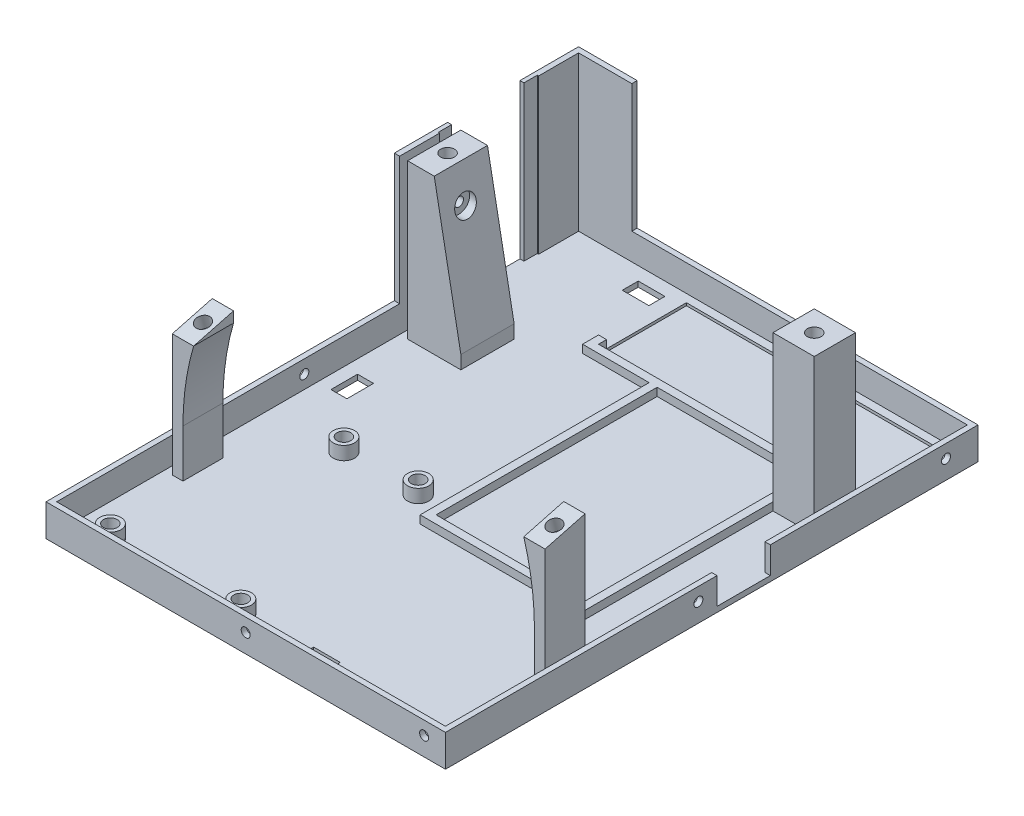
SolidWorks part; units mm, degrees
ref_plane "Front Plane" through (0, 0, 0) normal (0, 0, 1) x (1, 0, 0)
ref_plane "Top Plane" through (0, 0, 0) normal (0, 1, 0) x (1, 0, 0)
ref_plane "Right Plane" through (0, 0, 0) normal (1, 0, 0) x (0, 0, -1)
other "Configuration Table"
sketch "Sketch1" plane through (0, 0, 0) normal (0, 1, 0) x (1, 0, 0)
  line L1 (75, -100) -> (-75, -100)
  line L2 (75, -100) -> (75, 100)
  line L3 (75, 100) -> (-75, 100)
  line L4 (-75, -100) -> (-75, 100)
  line L5 (75, -100) -> (-75, 100) construction
  line L6 (75, 100) -> (-75, -100) construction
  point P0 (0, 0)
  dimension "D1" = 200
  dimension "D2" = 150
extrude "Boss-Extrude1" add sketch "Sketch1" along normal blind 2
sketch "Sketch2" plane through (0, 2, 0) normal (0, 1, 0) x (1, 0, 0)
  line L0 (75, 80) -> (-55, 80) construction
  line L1 (75, -100) -> (75, 100) construction
  line L2 (-55, 80) -> (-55, -100) construction
  line L3 (-75, -100) -> (75, -100) construction
  line L4 (75, 100) -> (-75, 100) construction
  line L5 (-65, -100) -> (-65, 100) construction
  line L6 (-75, 100) -> (-75, -100) construction
  line L7 (75, 90) -> (-75, 90) construction
  line L8 (-75, -80) -> (75, -80) construction
  line L9 (-75, -90) -> (75, -90) construction
  line L10 (-75, -100) -> (75, -100) construction
  line L11 (-62, 0) -> (-68, 0)
  line L12 (-62, 0) -> (-62, 10)
  line L13 (-62, 10) -> (-68, 10)
  line L14 (-68, 0) -> (-68, 10)
  line L15 (-62, 0) -> (-68, 10) construction
  line L16 (-62, 10) -> (-68, 0) construction
  line L18 (12.5, -93) -> (22.5, -93)
  line L19 (12.5, -93) -> (12.5, -87)
  line L20 (12.5, -87) -> (22.5, -87)
  line L21 (22.5, -93) -> (22.5, -87)
  line L22 (12.5, -93) -> (22.5, -87) construction
  line L23 (12.5, -87) -> (22.5, -93) construction
  line L24 (-35.5887, 87) -> (-45.5887, 87)
  line L25 (-35.5887, 87) -> (-35.5887, 93)
  line L26 (-35.5887, 93) -> (-45.5887, 93)
  line L27 (-45.5887, 87) -> (-45.5887, 93)
  line L28 (-35.5887, 87) -> (-45.5887, 93) construction
  line L29 (-35.5887, 93) -> (-45.5887, 87) construction
  point P22 (-40.5887, 90)
  dimension "D7" = 6
  dimension "D10" = 10
  dimension "D1" = 20
  dimension "D2" = 20
  dimension "D3" = 10
  dimension "D4" = 10
  dimension "D5" = 20
  dimension "D6" = 10
  dimension "D8" = 6
  dimension "D9" = 100
  dimension "D11" = 10
  dimension "D12" = 6
  dimension "D13" = 10
extrude "Cut-Extrude1" cut sketch "Sketch2" against normal through all
sketch "Sketch5" plane through (0, 2, 0) normal (0, 1, 0) x (1, 0, 0)
  line L0 (-75, 100) -> (-75, -100)
  line L1 (75, 100) -> (-75, 100) construction
  line L2 (-75, 100) -> (75, 100)
  line L3 (-73, 98) -> (73, 98)
  line L4 (-75, -100) -> (75, -100) construction
  line L5 (75, -100) -> (75, 100) construction
  line L6 (75, 100) -> (75, 98)
  line L8 (-73, 98) -> (-73, -98)
  line L10 (75, -98) -> (75, -100)
  line L11 (75, -100) -> (-75, -100)
  line L12 (-73, -98) -> (73, -98)
  line L13 (73, 98) -> (73, -98)
  line L14 (75, 98) -> (75, -98)
  line L15 (-75, 100) -> (-75, -100) construction
  dimension "D1" = 0
  dimension "D2" = 0
  dimension "D3" = 2
  dimension "D4" = 2
  dimension "D5" = 2
  dimension "D6" = 2
  dimension "D7" = 0
extrude "Boss-Extrude2" add sketch "Sketch5" along normal blind 10
sketch "Sketch6" plane through (-75, 0, 0) normal (-1, 0, 0) x (0, 0, 1)
  line L1 (-80, 2) -> (100, 2) construction
  line L3 (-50.8, 2) -> (-78, 2)
  line L4 (-100, 12) -> (-100, 0) construction
  line L5 (-78, 2) -> (-78, 12)
  line L6 (-100, 12) -> (100, 12) construction
  line L7 (-78, 12) -> (-50.8, 12)
  line L8 (-50.8, 12) -> (-50.8, 2)
  dimension "D1" = 27.2
  dimension "D2" = 22
extrude "Cut-Extrude2" cut sketch "Sketch6" against normal blind 10
sketch "Sketch8" plane through (-75, 0, 0) normal (-1, 0, 0) x (0, 0, 1)
  line L2 (100, 12) -> (100, 0) construction
  circle A1 centre (5, 7) radius 1.7
  dimension "D3" = 95
extrude "Cut-Extrude4" cut sketch "Sketch8" against normal through all
sketch "Sketch10" plane through (75, 0, 0) normal (1, 0, 0) x (0, 0, -1)
  line L2 (-100, 2) -> (100, 2) construction
  line L3 (2, 2) -> (2, 12)
  line L4 (-100, 12) -> (100, 12) construction
  line L5 (2, 12) -> (22, 12)
  line L6 (22, 12) -> (22, 2)
  line L8 (2, 2) -> (22, 2)
  line L9 (-100, 12) -> (-100, 0) construction
  dimension "D1" = 20
  dimension "D2" = 102
extrude "Cut-Extrude6" cut sketch "Sketch10" against normal blind 10
sketch "Sketch12" plane through (0, 2, 0) normal (0, 1, 0) x (1, 0, 0)
  line L0 (-63, -92) -> (-9.7, -92) construction
  line L1 (56, 95) -> (56, 62) construction
  line L2 (56, 62) -> (-29, 62) construction
  line L3 (-29, 62) -> (-29, 95) construction
  line L4 (-73, -98) -> (73, -98) construction
  line L5 (-9.7, -92) -> (-9.7, -23.4) construction
  line L6 (-9.7, -23.4) -> (-63, -23.4) construction
  line L7 (73, 22) -> (73, 98) construction
  line L8 (-73, 50.8) -> (-73, -98) construction
  line L9 (-63, -23.4) -> (-63, -92) construction
  line L10 (63, -92) -> (9.3, -92) construction
  line L11 (73, -98) -> (73, 2) construction
  line L12 (9.3, -92) -> (9.3, -10.6) construction
  line L13 (9.3, -10.6) -> (63, -10.6) construction
  line L14 (63, -10.6) -> (63, -92) construction
  line L15 (-29, 95) -> (56, 95) construction
  line L16 (73, 98) -> (-73, 98) construction
  line L17 (-53.4, -92) -> (-53.4, -100) construction
  line L18 (-75, -100) -> (75, -100) construction
  line L19 (-53.4, -100) -> (-41.4, -100) construction
  line L20 (-41.4, -100) -> (-41.4, -92) construction
  line L21 (-73, 78) -> (-73, 50.8) construction
  dimension "D1" = 6
  dimension "D2" = 33
  dimension "D3" = 10
  dimension "D4" = 53.3
  dimension "D5" = 10
  dimension "D6" = 68.6
  dimension "D7" = 81.4
  dimension "D8" = 53.7
  dimension "D9" = 3
  dimension "D10" = 85
  dimension "D11" = 17
  dimension "D12" = 12
  dimension "D13" = 9.6
sketch "Sketch15" plane through (0, 0, 100) normal (0, 0, 1) x (1, 0, 0)
  line L0 (-75, 0) -> (75, 0) construction
  line L2 (75, 12) -> (75, 0) construction
  circle A0 centre (0, 7) radius 1.7
  dimension "D1" = 7
  dimension "D2" = 75
extrude "Cut-Extrude7" cut sketch "Sketch15" against normal blind 10
sketch "Sketch16" plane through (0, 0, 100) normal (0, 0, 1) x (1, 0, 0)
  line L0 (-75, 0) -> (75, 0) construction
  circle A0 centre (67, 7) radius 1.7
  dimension "D1" = 8
  dimension "D2" = 7
extrude "Cut-Extrude8" cut sketch "Sketch16" against normal blind 3
sketch "Sketch19" plane through (0, 2, 0) normal (0, 1, 0) x (1, 0, 0)
  line L0 (-7.55, -94) -> (-65.15, -94) construction
  line L1 (-63, -23.4) -> (-63, -92) construction
  line L2 (-73, -98) -> (73, -98) construction
  line L3 (-65.15, -94) -> (-65.15, 4.3) construction
  line L4 (-65.15, 4.3) -> (-7.55, 4.3) construction
  line L5 (-7.55, 4.3) -> (-7.55, -94) construction
  circle A0 centre (-60.85, -90) radius 4
  circle A1 centre (-11.85, -90) radius 4
  circle A2 centre (-45.23, -17.9) radius 4
  circle A3 centre (-17.32, -17.9) radius 4
  point P17 (0, 0)
  dimension "D6" = 4
  dimension "D8" = 37.68
  dimension "D10" = 9.77
  dimension "D1" = 2.15
  dimension "D2" = 2.15
  dimension "D3" = 4
  dimension "D4" = 4.3
  dimension "D5" = 4
  dimension "D7" = 4.3
  dimension "D9" = 72.1
extrude "Boss-Extrude3" add sketch "Sketch19" along normal blind 5
sketch "Sketch20" plane through (0, 7, 0) normal (0, 1, 0) x (1, 0, 0)
  circle A0 centre (-45.23, -17.9) radius 2.6
  circle A1 centre (-17.32, -17.9) radius 2.6
  circle A2 centre (-11.85, -90) radius 2.6
  circle A3 centre (-60.85, -90) radius 2.6
extrude "Cut-Extrude10" cut sketch "Sketch20" against normal blind 5
sketch "Sketch21" plane through (0, 2, 0) normal (0, 1, 0) x (1, 0, 0)
  line L0 (-29.5, 65) -> (-32.5, 65)
  line L1 (73, 22) -> (73, 98) construction
  line L2 (-32.5, 65) -> (-32.5, 59)
  line L3 (-32.5, 59) -> (70, 59)
  line L8 (70, 62) -> (-29.5, 62)
  line L9 (-29.5, 62) -> (-29.5, 65)
  line L12 (70, 59) -> (70, 62)
  line L15 (-29, 62) -> (-29, 95) construction
  point P4 (-29.5, 63.5)
  dimension "D1" = 3
  dimension "D2" = 3
  dimension "D3" = 3
  dimension "D4" = 0.5
  dimension "D5" = 3
extrude "Boss-Extrude4" add sketch "Sketch21" along normal blind 3
sketch "Sketch22" plane through (0, 12, 0) normal (0, 1, 0) x (1, 0, 0)
  line L0 (-75, 50.8) -> (-73, 50.8)
  line L1 (-73, 50.8) -> (-73, 30.8)
  line L2 (-75, 100) -> (-53, 100)
  line L3 (-73, 30.8) -> (-75, 30.8)
  line L4 (-75, 50.8) -> (-75, -100) construction
  line L5 (-75, 30.8) -> (-75, 50.8)
  line L7 (75, 100) -> (-75, 100) construction
  line L9 (-75, 100) -> (-75, 78) construction
  line L10 (-75, 100) -> (-75, 78)
  line L11 (-75, 78) -> (-73, 78)
  line L12 (-53, 100) -> (-53, 98)
  line L13 (73, 98) -> (-73, 98) construction
  line L14 (-53, 98) -> (-73, 98)
  line L15 (-73, 98) -> (-73, 78)
  dimension "D1" = 22
  dimension "D2" = 20
  dimension "D3" = 2
  dimension "D4" = 2
extrude "Boss-Extrude5" add sketch "Sketch22" along normal blind 48
sketch "Sketch25" plane through (0, 60, 0) normal (0, 1, 0) x (1, 0, 0)
  line L0 (-73, 78) -> (-73, 83)
  line L2 (-73, 83) -> (-73.5, 83)
  line L3 (-73.5, 83) -> (-73.5, 78)
  line L5 (-73.5, 78) -> (-73, 78)
  line L12 (-73, 50.8) -> (-73.5, 50.8)
  line L13 (-73, 50.8) -> (-75, 50.8) construction
  line L14 (-73.5, 50.8) -> (-73.5, 45.8)
  line L15 (-73.5, 45.8) -> (-73, 45.8)
  line L16 (-73, 50.8) -> (-73, -98) construction
  line L17 (-73, 45.8) -> (-73, 50.8)
  dimension "D1" = 0.5
  dimension "D2" = 5
  dimension "D3" = 5
extrude "Cut-Extrude13" cut sketch "Sketch25" against normal up to surface (58 mm away) up to face at (-17.32, 2, 21.9)
sketch "Sketch26" plane through (75, 0, 0) normal (1, 0, 0) x (0, 0, -1)
  line L0 (-100, 0) -> (100, 0) construction
  line L1 (100, 12) -> (100, 0) construction
  circle A0 centre (88, 7) radius 1.7
  point P5 (0, 0)
  dimension "D1" = 7
  dimension "D2" = 12
extrude "Cut-Extrude15" cut sketch "Sketch26" against normal blind 5
sketch "Sketch27" plane through (0, 2, 0) normal (0, 1, 0) x (1, 0, 0)
  line L0 (-70, 50.8) -> (-70, 30.8)
  line L1 (-70, 30.8) -> (-50, 30.8)
  line L2 (-50, 30.8) -> (-50, 50.8)
  line L3 (-50, 50.8) -> (-70, 50.8)
  line L5 (-73, 45.8) -> (-73, -98) construction
  point P2 (0, 0)
  point P5 (0, 0)
  point P6 (0, 0)
  point P11 (0, 0)
  point P13 (0, 0)
  dimension "D1" = 3
  dimension "D2" = 20
extrude "Boss-Extrude6" add sketch "Sketch27" along normal blind 5
sketch "Sketch28" plane through (0, 0, -30.8) normal (0, 0, 1) x (1, 0, 0)
  line L0 (-70, 7) -> (-70, 60)
  line L1 (-70, 60) -> (-60, 60)
  line L2 (-60, 60) -> (-50, 7)
  line L3 (-50, 7) -> (-70, 7)
  point P3 (0, 0)
  dimension "D1" = 10
extrude "Boss-Extrude7" add sketch "Sketch28" against normal up to vertex (20 mm away) up to point (-50, 7, -50.8)
sketch "Sketch29" plane through (-50, 0, 0) normal (1, 0, 0) x (0, 0, -1)
  line L0 (30.8, 2) -> (50.8, 2) construction
  circle A0 centre (40.0878, 47) radius 4
  dimension "D1" = 45
extrude "Cut-Extrude16" cut sketch "Sketch29" against normal up to vertex (10 mm away) up to point (-60, 60, -30.8)
sketch "Sketch31" plane through (-60, 0, 0) normal (1, 0, 0) x (0, 0, -1)
  line L0 (40.0878, 43) -> (40.0878, 51) construction
  circle A0 centre (40.0878, 47) radius 4 construction
  circle A1 centre (40.0878, 47) radius 4 construction
  circle A2 centre (40.0878, 47) radius 1.7
extrude "Cut-Extrude17" cut sketch "Sketch31" against normal through all
sketch "Sketch34" plane through (0, 2, 0) normal (0, 1, 0) x (1, 0, 0)
  line L0 (-4.5, 59) -> (-4.5, -24)
  line L1 (-32.5, 59) -> (70, 59) construction
  line L2 (-4.5, -24) -> (51.5, -24)
  line L3 (51.5, -24) -> (51.5, 59)
  line L4 (-32.5, 59) -> (70, 59) construction
  line L5 (51.5, 59) -> (54.5, 59)
  line L6 (54.5, 59) -> (54.5, -27)
  line L7 (54.5, -27) -> (-7.5, -27)
  line L8 (-7.5, -27) -> (-7.5, 59)
  line L9 (-7.5, 59) -> (-4.5, 59)
  dimension "D1" = 83
  dimension "D2" = 3
  dimension "D3" = 3
  dimension "D4" = 56
  dimension "D5" = 25
  dimension "D6" = 3
extrude "Boss-Extrude9" add sketch "Sketch34" along normal blind 3
sketch "Sketch35" plane through (0, 2, 0) normal (0, 1, 0) x (1, 0, 0)
  line L0 (54.5, 59) -> (70, 59)
  line L1 (70, 59) -> (70, 43.5)
  line L2 (70, 43.5) -> (54.5, 43.5)
  line L3 (54.5, -27) -> (54.5, 59) construction
  line L4 (54.5, 43.5) -> (54.5, 59)
extrude "Boss-Extrude10" add sketch "Sketch35" along normal up to vertex (58 mm away) up to point (-60, 60, -30.8)
sketch "Sketch36" plane through (0, 60, 0) normal (0, 1, 0) x (1, 0, 0)
  line L0 (54.5, 59) -> (70, 43.5) construction
  circle A0 centre (62.25, 51.25) radius 2.6
extrude "Cut-Extrude20" cut sketch "Sketch36" against normal blind 5
sketch "Sketch37" plane through (0, 2, 0) normal (0, 1, 0) x (1, 0, 0)
  line L0 (-70, -42.5731) -> (-70, -57.5731)
  line L1 (-70, -57.5731) -> (-66, -57.5731)
  line L2 (-66, -57.5731) -> (-66, -42.5731)
  line L3 (-66, -42.5731) -> (-70, -42.5731)
  line L4 (-73, 30.8) -> (-73, -98) construction
  line L5 (-63, -23.4) -> (-63, -92) construction
  line L6 (70, -42.5731) -> (66, -42.5731)
  line L7 (66, -42.5731) -> (66, -57.5731)
  line L8 (66, -57.5731) -> (70, -57.5731)
  line L9 (70, -57.5731) -> (70, -42.5731)
  line L10 (73, -98) -> (73, 2) construction
  dimension "D1" = 3
  dimension "D2" = 3
  dimension "D3" = 3
  dimension "D4" = 15
sketch "Sketch38" plane through (0, 60, 0) normal (0, 1, 0) x (1, 0, 0)
  line L0 (-70, 50.8) -> (-60, 30.8) construction
  circle A0 centre (-65, 40.8) radius 2.6
extrude "Cut-Extrude21" cut sketch "Sketch38" against normal blind 5
extrude "Boss-Extrude11" add sketch "Sketch37" along normal blind 45.92
sketch "Sketch39" plane through (-66, 0, 0) normal (1, 0, 0) x (0, 0, -1)
  line L0 (-42.5731, 47.92) -> (-42.5731, 51.89) construction
  line L1 (-42.5731, 51.89) -> (-57.5731, 47.92) construction
  line L2 (-57.5731, 47.92) -> (-42.5731, 47.92)
  line L3 (-42.5731, 47.92) -> (-42.5731, 51.89)
  line L4 (-42.5731, 51.89) -> (-57.5731, 47.92)
  dimension "D1" = 3.97
extrude "Boss-Extrude12" add sketch "Sketch39" against normal blind 4 and the other way blind 4
fillet "Fillet1" radius 100 1 edges at (-66, 47.92, 50.0731)
sketch "Sketch40" plane through (70, 0, 0) normal (1, 0, 0) x (0, 0, -1)
  line L0 (-42.5731, 47.92) -> (-42.5731, 51.89)
  line L1 (-42.5731, 51.89) -> (-57.5731, 47.92)
  line L2 (-57.5731, 47.92) -> (-42.5731, 47.92)
extrude "Boss-Extrude13" add sketch "Sketch40" against normal blind 8
fillet "Fillet2" radius 100 1 edges at (66, 47.92, 50.0731)
sketch "Sketch41" plane through (0, 59.0232, 15.6215) normal (0, 0.9667, 0.2559) x (1, 0, 0)
  line L0 (-70, -27.8796) -> (-62, -43.3961) construction
  line L1 (70, -27.8796) -> (62, -43.3961) construction
  circle A0 centre (-66, -35.6379) radius 2.6
  circle A1 centre (66, -35.6379) radius 2.6
extrude "Cut-Extrude22" cut sketch "Sketch41" against normal blind 5
sketch "Sketch42" plane through (0, 2, 0) normal (0, 1, 0) x (1, 0, 0)
  line L0 (-29.5, 62) -> (-29.5, 95)
  line L1 (-29.5, 95) -> (70, 95)
  line L2 (70, 95) -> (70, 62)
  line L4 (70, 62) -> (-29.5, 62)
  point P4 (0, 0)
  point P6 (0, 0)
extrude "Cut-Extrude23" cut sketch "Sketch42" against normal blind 1
